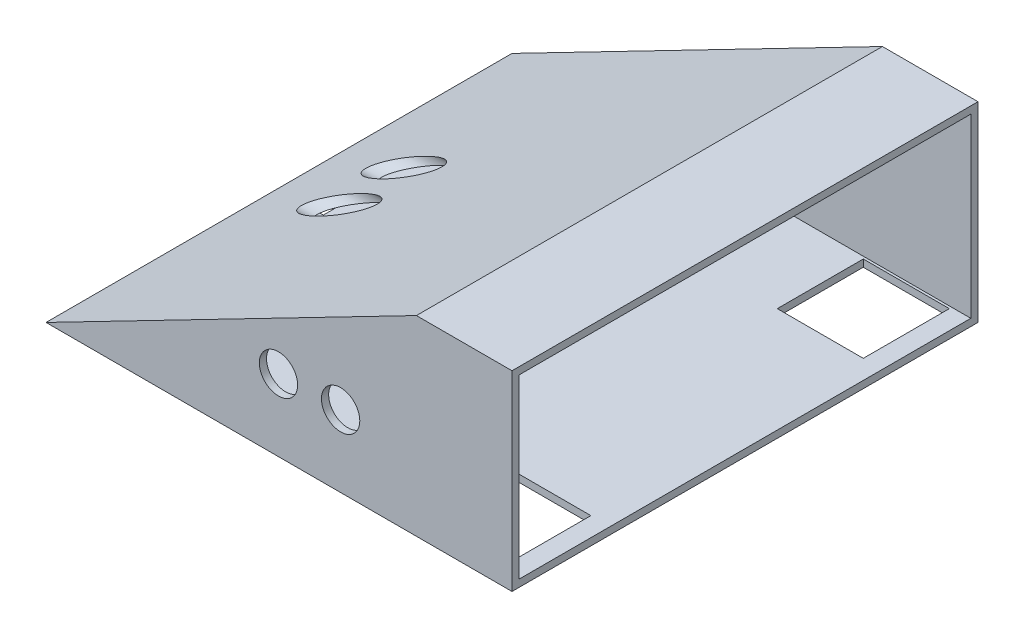
SolidWorks part; units mm, degrees
ref_plane "Front Plane" through (0, 0, 0) normal (0, 0, 1) x (1, 0, 0)
ref_plane "Top Plane" through (0, 0, 0) normal (0, 1, 0) x (1, 0, 0)
ref_plane "Right Plane" through (0, 0, 0) normal (1, 0, 0) x (0, 0, -1)
ref_plane "Plane1" through (0, 0, 0) normal (1, 0, 0) x (0, 0, -1)
ref_plane "Plane2" through (0, 0, 97.5) normal (0, 0, 1) x (1, 0, 0)
ref_plane "Plane3" through (75, 0, 0) normal (1, 0, 0) x (0, 0, -1)
sketch "Sketch2" plane through (0, 0, 0) normal (0, 0, 1) x (1, 0, 0)
  line L0 (0, 0) -> (195, 0)
  line L1 (195, 0) -> (195, 80)
  line L2 (195, 80) -> (155, 80)
  line L3 (155, 80) -> (0, 0)
  dimension "D1" = 195
  dimension "D2" = 40
  dimension "80" = 80
extrude "Robot" add sketch "Sketch2" along normal blind 195
sketch "Sketch3" plane through (0, 0, 195) normal (0, 0, 1) x (1, 0, 0)
  line L0 (0, 0) -> (195, 0) construction
  circle A0 centre (97.2899, 30) radius 8.02
  circle A1 centre (123.2899, 30) radius 8.02
  dimension "D1" = 30
  dimension "D2" = 16.04
  dimension "D4" = 16.04
  dimension "D3" = 26
  dimension "D5" = 30
sketch "Arriba" plane through (0, 80, 0) normal (0, 1, 0) x (1, 0, 0)
  line L0 (195, 0) -> (195, -195) construction
  line L1 (0, 0) -> (0, -195) construction
  line L2 (0, -97.5) -> (195, -97.5) construction
  line L3 (0, 0) -> (195, 0) construction
  line L4 (0, -195) -> (195, -195) construction
  line L5 (97.5, 0) -> (97.5, -195) construction
sketch "Adelante" plane through (0, 0, 0) normal (1, 0, 0) x (0, 0, -1)
  line L0 (0, 80) -> (0, 0) construction
  line L1 (-97.5, 80) -> (-97.5, 0) construction
  line L2 (0, 80) -> (-195, 80) construction
  line L3 (-195, 0) -> (0, 0) construction
  line L4 (-195, 80) -> (-195, 0) construction
  line L5 (0, 0) -> (-195, 0) construction
sketch "Sketch9" plane through (0, 0, 0) normal (0, 0, -1) x (-1, 0, 0)
  line L1 (0, 0) -> (-195, 0) construction
  circle A0 centre (-97.284, 30) radius 8.2
  circle A1 centre (-123.284, 30) radius 8.2
  dimension "D2" = 16.4
  dimension "D4" = 30
  dimension "D6" = 16.4
  dimension "D3" = 30
  dimension "D5" = 26
sketch "Sketch10" plane through (0, 0, 0) normal (0, -1, 0) x (-1, 0, 0)
  line L0 (0, -195) -> (-195, -195) construction
  line L1 (-187, -191) -> (-150, -191)
  line L2 (-187, -191) -> (-187, -154)
  line L3 (-187, -154) -> (-150, -154)
  line L4 (-150, -191) -> (-150, -154)
  line L5 (-195, 0) -> (-195, -195) construction
  dimension "D1" = 4
  dimension "D2" = 8
  dimension "D3" = 37
  dimension "D4" = 37
sketch "Sketch12" plane through (0, 0, 0) normal (0, -1, 0) x (-1, 0, 0)
  line L0 (-195, 0) -> (-195, -195) construction
  line L1 (-187, -40) -> (-151, -40)
  line L2 (-187, -40) -> (-187, -4)
  line L3 (-187, -4) -> (-151, -4)
  line L4 (-151, -40) -> (-151, -4)
  line L5 (0, 0) -> (-195, 0) construction
  dimension "D1" = 8
  dimension "D2" = 4
  dimension "D3" = 36
  dimension "D4" = 36
sketch "Sketch13" plane through (0, 0, 0) normal (0, -1, 0) x (1, 0, 0)
  line L0 (0, 0) -> (195, 0) construction
  line L1 (15, 8) -> (22.1, 8)
  line L2 (15, 8) -> (15, 15.1)
  line L3 (15, 15.1) -> (22.1, 15.1)
  line L4 (22.1, 8) -> (22.1, 15.1)
  line L5 (0, 0) -> (0, 195) construction
  dimension "D1" = 8
  dimension "D2" = 15
  dimension "D3" = 7.1
  dimension "D4" = 7.1
sketch "Sketch14" plane through (0, 0, 0) normal (0, -1, 0) x (-1, 0, 0)
  line L0 (0, -195) -> (-195, -195) construction
  line L1 (-15, -179.9) -> (-22.1, -179.9)
  line L2 (-15, -179.9) -> (-15, -187)
  line L3 (-15, -187) -> (-22.1, -187)
  line L4 (-22.1, -179.9) -> (-22.1, -187)
  line L5 (0, 0) -> (0, -195) construction
  dimension "D1" = 8
  dimension "D2" = 15
  dimension "D3" = 7.1
  dimension "D4" = 7.1
sketch "Sketch15" plane through (0, 0, 0) normal (0, -1, 0) x (-1, 0, 0)
  line L0 (0, -97.5) -> (-195, -97.5) construction
  line L1 (-15, -93.95) -> (-22.1, -93.95)
  line L2 (-15, -93.95) -> (-15, -101.05)
  line L3 (-15, -101.05) -> (-22.1, -101.05)
  line L4 (-22.1, -93.95) -> (-22.1, -101.05)
  line L5 (0, 0) -> (0, -195) construction
  dimension "D1" = 3.55
  dimension "D2" = 3.55
  dimension "D3" = 7.1
  dimension "D4" = 15
shell "Vacio por dentro 3mm" thickness 3 removed face at (195, 40, 97.5)
extrude "Ultrasonico Derecha" cut sketch "Sketch3" against normal blind 3
sketch "Ultrasonico Centro " plane through (0, 0, 0) normal (1, 0, 0) x (0, 0, -1)
  line L0 (0, 0) -> (-195, 0) construction
  line L1 (-97.5, 80) -> (-97.5, 0) construction
  circle A0 centre (-84, 20) radius 8.2
  circle A1 centre (-111, 20) radius 8.2
  dimension "D2" = 16.4
  dimension "D4" = 16.4
  dimension "D1" = 20
  dimension "D3" = 13.5
  dimension "D5" = 13.5
  dimension "D6" = 20
extrude "Ultrasonico Izquierda" cut sketch "Sketch9" against normal blind 3
extrude "Rueda Derecha" cut sketch "Sketch10" against normal blind 3
extrude "Rueda Izquierda" cut sketch "Sketch12" against normal blind 3
extrude "Cyn70 Derecha" cut sketch "Sketch14" against normal blind 4
extrude "Cny70 Centro" cut sketch "Sketch15" against normal blind 4
extrude "Cny70 Izquierda" cut sketch "Sketch13" against normal blind 4
extrude "Cut-Extrude4" cut sketch "Ultrasonico Centro " along normal blind 75
